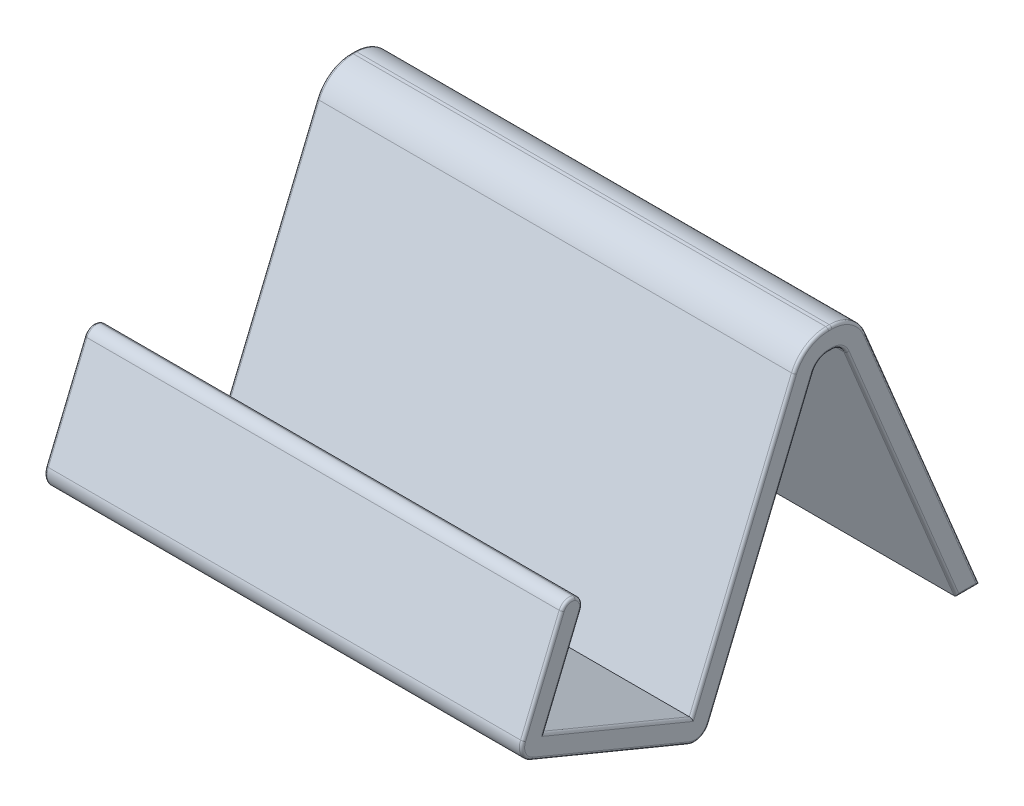
SolidWorks part; units mm, degrees
ref_plane "Front Plane" through (0, 0, 0) normal (0, 0, 1) x (1, 0, 0)
ref_plane "Top Plane" through (0, 0, 0) normal (0, 1, 0) x (1, 0, 0)
ref_plane "Right Plane" through (0, 0, 0) normal (1, 0, 0) x (0, 0, -1)
sketch "Sketch1" plane through (0, 0, 0) normal (1, 0, 0) x (0, 0, -1)
  line L0 (-20.0627, 29.9581) -> (-27.7164, 11.4805)
  line L1 (-27.7164, 11.4805) -> (0, 0)
  line L2 (0, 0) -> (21.0476, 50.8134)
  line L3 (21.0476, 50.8134) -> (31.0476, 50.8134)
  line L4 (31.0476, 50.8134) -> (53.6259, -3.6955)
  line L5 (26.0476, 50.8134) -> (26.0476, -28.1173) construction
  line L6 (-23.7582, 31.4888) -> (-32.9426, 9.3157)
  line L7 (-32.9426, 9.3157) -> (2.1648, -5.2263)
  line L8 (2.1648, -5.2263) -> (23.7203, 46.8134)
  line L9 (23.7203, 46.8134) -> (28.3749, 46.8134)
  line L10 (28.3749, 46.8134) -> (49.9304, -5.2263)
  line L11 (-23.7582, 31.4888) -> (-20.0627, 29.9581)
  line L12 (49.9304, -5.2263) -> (54.26, -5.2263)
  line L13 (54.26, -5.2263) -> (53.6259, -3.6955)
  dimension "D1" = 55
  dimension "D2" = 20
  dimension "D3" = 45
  dimension "D4" = 22.5
  dimension "D5" = 10
  dimension "D6" = 30
  dimension "D7" = 4
extrude "Boss-Extrude1" add sketch "Sketch1" along normal mid plane 90
fillet "Fillet1" radius 7 2 edges at (0, 50.8134, -21.0476) (0, 50.8134, -31.0476)
fillet "Fillet3" radius 3 2 edges at (0, 46.8134, -28.3749) (0, 46.8134, -23.7203)
fillet "Fillet4" radius 3 2 edges at (0, -5.2263, -2.1648) (0, 9.3157, 32.9426)
fillet "Fillet5" radius 2 2 edges at (0, 29.9581, 20.0627) (0, 31.4888, 23.7582)
fillet "Fillet6" radius 0.5 38 edges at (-45, 20.8642, 28.1591) (-45, 9.7913, 31.7946) (-45, 2.0447, 15.3889) (-45, -4.0782, -1.6892) (-45, 21.2534, -13.133) (-45, 46.3078, -24.0581) (-45, 46.8134, -26.0476) (-45, 46.3078, -28.037) (-45, 19.8676, -39.5362) (-45, -5.2263, -52.0952) (-45, 20.633, -43.5487) (-45, 49.6337, -30.2593) (-45, 50.8134, -26.0476) (-45, 49.6337, -21.8358) (-45, 23.2461, -9.6288) (-45, 5.7403, 13.8582) (-45, 19.7954, 24.2722) (-45, 29.6411, 20.8281) (-45, 30.7235, 23.4412) (45, 5.7403, 13.8582) (45, 23.2461, -9.6288) (45, 49.6337, -21.8358) (45, 50.8134, -26.0476) (45, 49.6337, -30.2593) (45, 20.633, -43.5487) (45, -5.2263, -52.0952) (45, 19.8676, -39.5362) (45, 46.3078, -28.037) (45, 46.8134, -26.0476) (45, 46.3078, -24.0581) (45, 21.2534, -13.133) (45, -4.0782, -1.6892) (45, 2.0447, 15.3889) (45, 9.7913, 31.7946) (45, 20.8642, 28.1591) (45, 30.7235, 23.4412) (45, 29.6411, 20.8281) (45, 19.7954, 24.2722)
equation "\"D4@Sketch1\"=\"D3@Sketch1\"/2"
